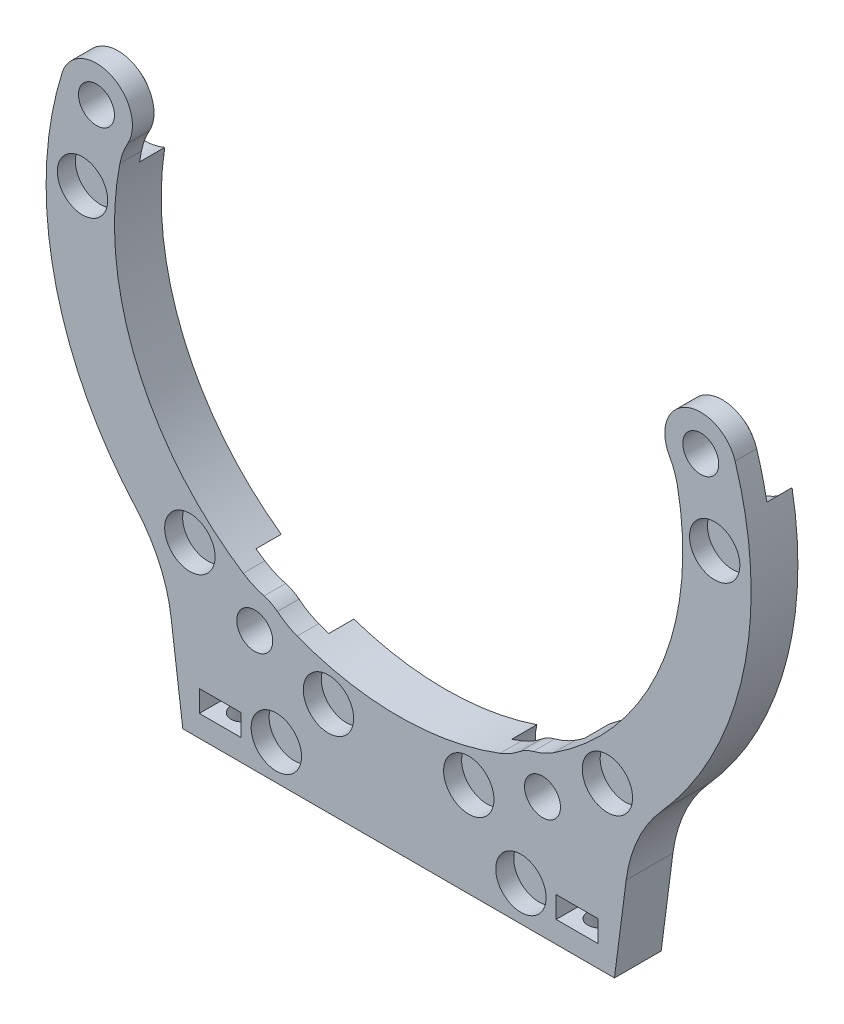
SolidWorks part; units mm, degrees
ref_plane "Front Plane" through (0, 0, 0) normal (0, 0, 1) x (1, 0, 0)
ref_plane "Top Plane" through (0, 0, 0) normal (0, 1, 0) x (1, 0, 0)
ref_plane "Right Plane" through (0, 0, 0) normal (1, 0, 0) x (0, 0, -1)
sketch "Sketch1" plane through (0, 0, 0) normal (0, 0, 1) x (1, 0, 0)
  line L0 (-30, -56) -> (-32.5, -36.6708) construction
  line L1 (-30, -56) -> (30, -56) construction
  line L2 (30, -56) -> (32.5, -36.6708) construction
  line L3 (-30, -56) -> (-32.5, -36.6708)
  line L4 (-30, -56) -> (30, -56)
  line L5 (30, -56) -> (32.5, -36.6708)
  arc A0 (-38.2683, 9.787) -> (-19.7687, -34.1972) centre (0, 0) ccw construction
  circle A1 centre (-20, -39.1918) radius 7.5
  circle A2 centre (-20, -39.1918) radius 7.5
  circle A3 centre (20, -39.1918) radius 7.5
  circle A4 centre (20, -39.1918) radius 7.5
  circle A5 centre (42, 13.1149) radius 7.5
  circle A6 centre (42, 13.1149) radius 7.5
  circle A7 centre (-42, 13.1149) radius 7.5
  circle A8 centre (-42, 13.1149) radius 7.5
  arc A9 (-46.7727, 14.6052) -> (-32.5, -36.6708) centre (0, 0) ccw construction
  arc A10 (32.5, -36.6708) -> (46.7727, 14.6052) centre (0, 0) ccw construction
  arc A11 (-16.0913, -36.0738) -> (16.0913, -36.0738) centre (0, 0) ccw construction
  arc A12 (19.7687, -34.1972) -> (38.2683, 9.787) centre (0, 0) ccw construction
  arc A13 (-38.2683, 9.787) -> (-19.7687, -34.1972) centre (0, 0) ccw
  arc A14 (-46.7727, 14.6052) -> (-32.5, -36.6708) centre (0, 0) ccw
  arc A15 (32.5, -36.6708) -> (46.7727, 14.6052) centre (0, 0) ccw
  arc A16 (-16.0913, -36.0738) -> (16.0913, -36.0738) centre (0, 0) ccw
  arc A17 (19.7687, -34.1972) -> (38.2683, 9.787) centre (0, 0) ccw
  dimension "D1" = 0
  dimension "D2" = 0
  dimension "D3" = 0
  dimension "D4" = 0
extrude "Boss-Extrude1" add sketch "Sketch1" along normal offset from surface (3.5 mm away) 0.8 contours A17 A4 A16 A2 A13 A8 A14 L3 L4 L5 A15 A6 region at (-30.0844, -46.1847, 0) offset beyond the face yes
sketch "Sketch2" plane through (0, 0, 3.5) normal (0, 0, 1) x (1, 0, 0)
  line L0 (30, -56) -> (32.5, -36.6708) construction
  line L1 (-30, -56) -> (30, -56) construction
  line L2 (-30, -56) -> (-32.5, -36.6708) construction
  line L3 (30, -56) -> (32.5, -36.6708)
  line L4 (-30, -56) -> (30, -56)
  line L5 (-30, -56) -> (-32.5, -36.6708)
  circle A1 centre (-20, -39.1918) radius 5
  circle A2 centre (-20, -39.1918) radius 5
  circle A3 centre (-42, 13.1149) radius 5
  circle A4 centre (-42, 13.1149) radius 5
  circle A5 centre (42, 13.1149) radius 5
  circle A6 centre (42, 13.1149) radius 5
  circle A7 centre (0, 0) radius 49
  circle A8 centre (0, 0) radius 49
  circle A9 centre (0, 0) radius 39.5
  circle A10 centre (0, 0) radius 39.5
  circle A11 centre (-20, -39.1918) radius 2.5
  circle A12 centre (-20, -39.1918) radius 2.5
  circle A13 centre (20, -39.1918) radius 2.5
  circle A14 centre (20, -39.1918) radius 2.5
  circle A15 centre (42, 13.1149) radius 2.5
  circle A16 centre (42, 13.1149) radius 2.5
  circle A17 centre (-42, 13.1149) radius 2.5
  circle A18 centre (-42, 13.1149) radius 2.5
  circle A19 centre (20, -39.1918) radius 5
  circle A20 centre (20, -39.1918) radius 5
  arc M11 (39.0041, 6.2392) -> (22.8191, -32.2418) centre (0, 0) cw
  arc M12 (22.8191, -32.2418) -> (12.718, -37.3965) centre (20, -39.1918) cw
  arc M13 (12.718, -37.3965) -> (-12.718, -37.3965) centre (0, 0) cw
  arc M14 (-12.718, -37.3965) -> (-22.8191, -32.2418) centre (-20, -39.1918) cw
  arc M15 (-22.8191, -32.2418) -> (-39.0041, 6.2392) centre (0, 0) cw
  arc M16 (-39.0041, 6.2392) -> (-48.1889, 8.8785) centre (-42, 13.1149) cw
  arc M17 (-48.1889, 8.8785) -> (-32.5, -36.6708) centre (0, 0) ccw
  line M18 (-32.5, -36.6708) -> (-30, -56)
  line M19 (-30, -56) -> (30, -56)
  line M20 (30, -56) -> (32.5, -36.6708)
  arc M21 (32.5, -36.6708) -> (48.1889, 8.8785) centre (0, 0) ccw
  arc M22 (48.1889, 8.8785) -> (39.0041, 6.2392) centre (42, 13.1149) cw
  dimension "D1" = 0
  dimension "D2" = 0
  dimension "D3" = 0
  dimension "D4" = 0
  dimension "D5" = 0
  dimension "D6" = 0
  dimension "D7" = 0
  dimension "D8" = 0
  dimension "D9" = 0
  dimension "D10" = 0
extrude "Boss-Extrude2" add sketch "Sketch2" along normal blind 3 contours A8 M17 M14 M15 M16 | A10 A4 A8 M16 | A10 A4 A18 | A4 A10 | A8 M18 M19 M20 M12 M14 | A8 M14 | A10 A8 A2 M14 | A10 A2 A12 | A10 A2 A8 M14 | A2 A10 | A8 M14 M12 M13 | A20 A10 A8 M12 | A8 M12 | A20 A8 A10 M12 | A10 A20 A14 | A10 A20 | A8 M12 M21 M22 M11 | A10 A8 A6 M22 | A10 A6 A16 | A6 A10 region at (0, -50.3667, 3.5) region at (38.9889, -16.3986, 3.5) region at (22.7027, -44.4879, 3.5) region at (24.8539, -36.855, 3.5) region at (-38.9889, -16.3986, 3.5) region at (43.7245, 8.0112, 3.5) region at (15.2596, -41.7511, 3.5) region at (16.2364, -42.2644, 3.5) region at (0, -43.7518, 3.5) region at (-43.7245, 8.0112, 3.5) region at (-24.8539, -36.855, 3.5) region at (-22.7027, -44.4879, 3.5) region at (46.8033, 13.8474, 3.5) region at (17.8584, -34.9951, 3.5) region at (-15.2596, -41.7511, 3.5) region at (-41.5639, 17.9541, 3.5) region at (-24.6964, -37.9472, 3.5) region at (37.5026, 11.7105, 3.5) region at (-37.5026, 11.7105, 3.5) region at (-17.8584, -34.9951, 3.5)
sketch "Sketch3" plane through (0, 0, 3.5) normal (0, 0, -1) x (-1, 0, 0)
  circle A0 centre (-20, -39.1918) radius 2.5 construction
  circle A1 centre (20, -39.1918) radius 2.5 construction
  circle A2 centre (42, 13.1149) radius 2.5 construction
  circle A3 centre (-42, 13.1149) radius 2.5 construction
  circle A4 centre (-20, -39.1918) radius 2.5
  circle A5 centre (20, -39.1918) radius 2.5
  circle A6 centre (42, 13.1149) radius 2.5
  circle A7 centre (-42, 13.1149) radius 2.5
  circle A8 centre (-42, 13.1149) radius 4.5
  circle A9 centre (42, 13.1149) radius 4.5
  circle A10 centre (20, -39.1918) radius 4.5
  circle A11 centre (-20, -39.1918) radius 4.5
  dimension "D1" = 9
extrude "Boss-Extrude3" add sketch "Sketch3" along normal blind 0.8
chamfer "Chamfer1" distance 0.6 angle 45 4 edges at (15.5, -39.1918, 2.7) (-24.5, -39.1918, 2.7) (-46.5, 13.1149, 2.7) (37.5, 13.1149, 2.7)
fillet "Fillet1" radius 20 2 edges at (-32.5, -36.6708, 3.25) (32.5, -36.6708, 3.25)
fillet "Fillet2" radius 10 6 edges at (16.0913, -36.0738, 5) (19.7687, -34.1972, 5) (-19.7687, -34.1972, 5) (-16.0913, -36.0738, 5) (-38.2683, 9.787, 5) (38.2683, 9.787, 5)
sketch "Sketch4" plane through (0, -56, 0) normal (0, -1, 0) x (1, 0, 0)
  line L4 (24.8, 3.4) -> (-24.8, 3.4)
  line L5 (24.8, -3.7) -> (24.8, 3.4)
  line L6 (-24.8, -3.7) -> (24.8, -3.7)
  line L7 (-24.8, 3.4) -> (-24.8, -3.7)
  line L8 (24.8, 3.4) -> (-24.8, 3.4) construction
  line L9 (24.8, -3.7) -> (24.8, 3.4) construction
  line L10 (-24.8, -3.7) -> (24.8, -3.7) construction
  line L11 (-24.8, 3.4) -> (-24.8, -3.7) construction
  circle A1 centre (24.8, -3.7) radius 1.6
  circle A2 centre (24.8, -3.7) radius 1.6 construction
  circle A3 centre (-24.8, -3.7) radius 1.6
  circle A4 centre (-24.8, -3.7) radius 1.6 construction
  circle A5 centre (24.8, 3.4) radius 1.6
  circle A6 centre (24.8, 3.4) radius 1.6
  circle A7 centre (-24.8, 3.4) radius 1.6
  circle A8 centre (-24.8, 3.4) radius 1.6
  dimension "D1" = 0
  dimension "D2" = 0
  dimension "D3" = 0
  dimension "D4" = 0
  dimension "D5" = 0
extrude "Cut-Extrude1" cut sketch "Sketch4" against normal blind 9
ref_plane "Plane1" through (0, -53, 0) normal (0, -1, 0) x (-1, 0, 0)
sketch "Sketch5" plane through (0, -53, 0) normal (0, -1, 0) x (-1, 0, 0)
  line L7 (-27.7, 2.847) -> (-21.9, 2.847)
  line L8 (-27.7, 2.847) -> (-27.7, -9.647)
  line L9 (-27.7, -9.647) -> (-21.9, -9.647)
  line L10 (-21.9, 2.847) -> (-21.9, -9.647)
  line L11 (-27.7, 2.847) -> (-21.9, -9.647) construction
  line L12 (-27.7, -9.647) -> (-21.9, 2.847) construction
  line L13 (21.9, 3.8441) -> (27.7, 3.8441)
  line L14 (21.9, 3.8441) -> (21.9, -10.6441)
  line L15 (21.9, -10.6441) -> (27.7, -10.6441)
  line L16 (27.7, 3.8441) -> (27.7, -10.6441)
  line L17 (21.9, 3.8441) -> (27.7, -10.6441) construction
  line L18 (21.9, -10.6441) -> (27.7, 3.8441) construction
  point P0 (-24.8, -3.4)
  point P5 (24.8, -3.4)
  dimension "D1" = 5.8
extrude "Cut-Extrude2" cut sketch "Sketch5" against normal blind 3
sketch "Sketch6" plane through (0, 0, 6.5) normal (0, 0, 1) x (1, 0, 0)
  circle A1 centre (-29.0204, -33.0729) radius 1.6
  circle A2 centre (-29.0204, -33.0729) radius 1.6
  circle A3 centre (-43.9351, 2.388) radius 1.6
  circle A4 centre (-43.9351, 2.388) radius 1.6
  circle A5 centre (17, -51.1) radius 1.6
  circle A6 centre (17, -51.1) radius 1.6
  circle A7 centre (-17, -51.1) radius 1.6
  circle A8 centre (-17, -51.1) radius 1.6
  circle A9 centre (-9.7522, -42.9056) radius 1.6
  circle A10 centre (-9.7522, -42.9056) radius 1.6
  circle A11 centre (43.9351, 2.388) radius 1.6
  circle A12 centre (43.9351, 2.388) radius 1.6
  circle A13 centre (29.0204, -33.0729) radius 1.6
  circle A14 centre (29.0204, -33.0729) radius 1.6
  circle A15 centre (9.7522, -42.9056) radius 1.6
  circle A16 centre (9.7522, -42.9056) radius 1.6
  dimension "D1" = 0
  dimension "D2" = 0
  dimension "D3" = 0
  dimension "D4" = 0
  dimension "D5" = 0
  dimension "D6" = 0
  dimension "D7" = 0
  dimension "D8" = 0
extrude "Cut-Extrude3" cut sketch "Sketch6" against normal through all both and the other way through all
sketch "Sketch7" plane through (0, 0, 6.5) normal (0, 0, 1) x (1, 0, 0)
  circle A0 centre (-43.9351, 2.388) radius 3.5
  arc A1 (-46.7727, 14.6052) -> (-36.5477, -32.6384) centre (0, 0) ccw construction
  arc A2 (-38.7436, 7.6931) -> (-21.5978, -33.0724) centre (0, 0) ccw construction
  circle A3 centre (-29.0204, -33.0729) radius 3.5
  circle A4 centre (-9.7522, -42.9056) radius 3.5
  circle A5 centre (-17, -51.1) radius 3.5
  circle A6 centre (9.7522, -42.9056) radius 3.5
  circle A7 centre (17, -51.1) radius 3.5
  circle A8 centre (29.0204, -33.0729) radius 3.5
  circle A9 centre (43.9351, 2.388) radius 3.5
  dimension "D1" = 7
  dimension "D2" = 1.5
  dimension "D3" = 1
extrude "Cut-Extrude4" cut sketch "Sketch7" against normal blind 2.5
sketch "Sketch8" plane through (0, 0, 4) normal (0, 0, 1) x (1, 0, 0)
  circle A0 centre (43.9351, 2.388) radius 1.6 construction
  circle A1 centre (29.0204, -33.0729) radius 1.6 construction
  circle A2 centre (17, -51.1) radius 1.6 construction
  circle A3 centre (9.7522, -42.9056) radius 1.6 construction
  circle A4 centre (-17, -51.1) radius 1.6 construction
  circle A5 centre (-9.7522, -42.9056) radius 1.6 construction
  circle A6 centre (-29.0204, -33.0729) radius 1.6 construction
  circle A7 centre (-43.9351, 2.388) radius 1.6 construction
  circle A8 centre (43.9351, 2.388) radius 1.6
  circle A9 centre (29.0204, -33.0729) radius 1.6
  circle A10 centre (17, -51.1) radius 1.6
  circle A11 centre (9.7522, -42.9056) radius 1.6
  circle A12 centre (-17, -51.1) radius 1.6
  circle A13 centre (-9.7522, -42.9056) radius 1.6
  circle A14 centre (-29.0204, -33.0729) radius 1.6
  circle A15 centre (-43.9351, 2.388) radius 1.6
extrude "Boss-Extrude4" add sketch "Sketch8" against normal blind 0.3
